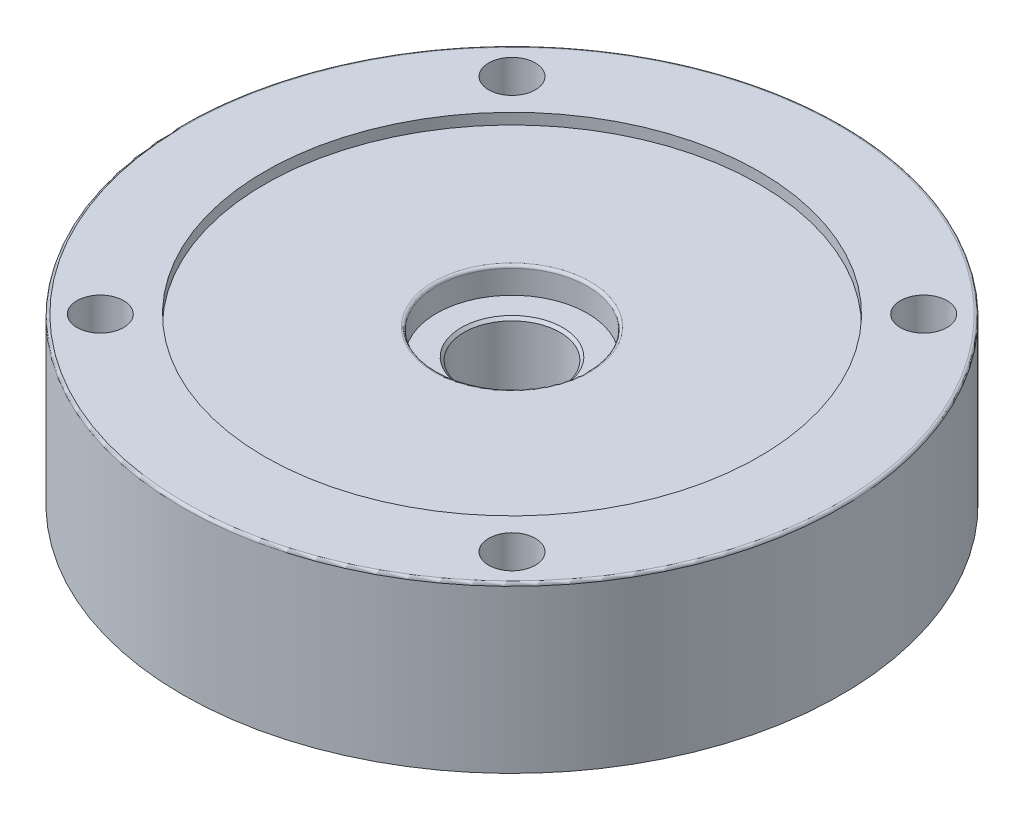
SolidWorks part; units mm, degrees
ref_plane "Front Plane" through (0, 0, 0) normal (0, 0, 1) x (1, 0, 0)
ref_plane "Top Plane" through (0, 0, 0) normal (0, 1, 0) x (1, 0, 0)
ref_plane "Right Plane" through (0, 0, 0) normal (1, 0, 0) x (0, 0, -1)
sketch "Sketch1" plane through (0, 0, 0) normal (0, 0, 1) x (1, 0, 0)
  line L0 (27.5, 0) -> (120, 0)
  line L1 (120, 0) -> (120, 60)
  line L2 (120, 60) -> (90, 60)
  line L3 (90, 60) -> (90, 56)
  line L4 (90, 56) -> (27.5, 56)
  line L5 (27.5, 56) -> (27.5, 0)
  line L6 (0, 0) -> (0, 58.1188) construction
  line L7 (37.5, 46.5) -> (17.5, 46.5)
  line L8 (37.5, 46.5) -> (37.5, 9.5)
  line L9 (37.5, 9.5) -> (17.5, 9.5)
  line L10 (17.5, 46.5) -> (17.5, 9.5)
  line L11 (37.5, 46.5) -> (17.5, 9.5) construction
  line L12 (37.5, 9.5) -> (17.5, 46.5) construction
  point P3 (27.5, 28)
  dimension "D1" = 27.5
  dimension "D2" = 120
  dimension "D3" = 90
  dimension "D4" = 4
  dimension "D5" = 60
  dimension "D6" = 17.5
  dimension "D7" = 9.5
revolve "Revolve1" add sketch "Sketch1" angle 360 about L6 region at (77.6065, 28.7302, 0) region at (22.5, 28, 0) region at (32.5, 28, 0)
ref_axis "Axis1" through (0, 60, 0) along (0, -1, 0)
sketch "Sketch2" plane through (0, 60, 0) normal (0, 1, 0) x (1, 0, 0)
  line L1 (74.9533, -74.9533) -> (-74.9533, -74.9533) construction
  line L2 (74.9533, -74.9533) -> (74.9533, 74.9533) construction
  line L3 (74.9533, 74.9533) -> (-74.9533, 74.9533) construction
  line L4 (-74.9533, -74.9533) -> (-74.9533, 74.9533) construction
  line L5 (74.9533, -74.9533) -> (-74.9533, 74.9533) construction
  line L6 (74.9533, 74.9533) -> (-74.9533, -74.9533) construction
  circle A0 centre (-74.9533, 74.9533) radius 8.5
  circle A1 centre (74.9533, 74.9533) radius 8.5
  circle A2 centre (74.9533, -74.9533) radius 8.5
  circle A3 centre (-74.9533, -74.9533) radius 8.5
  point P0 (0, 0)
  dimension "D2" = 17
  dimension "D1" = 149.9066
extrude "Cut-Extrude1" cut sketch "Sketch2" against normal through all
fillet "Fillet1" radius 1 2 edges at (0, 56, -27.5) (0, 60, -120)
chamfer "Chamfer1" distance 1 angle 45 2 edges at (0, 9.5, -17.5) (0, 46.5, -17.5)
